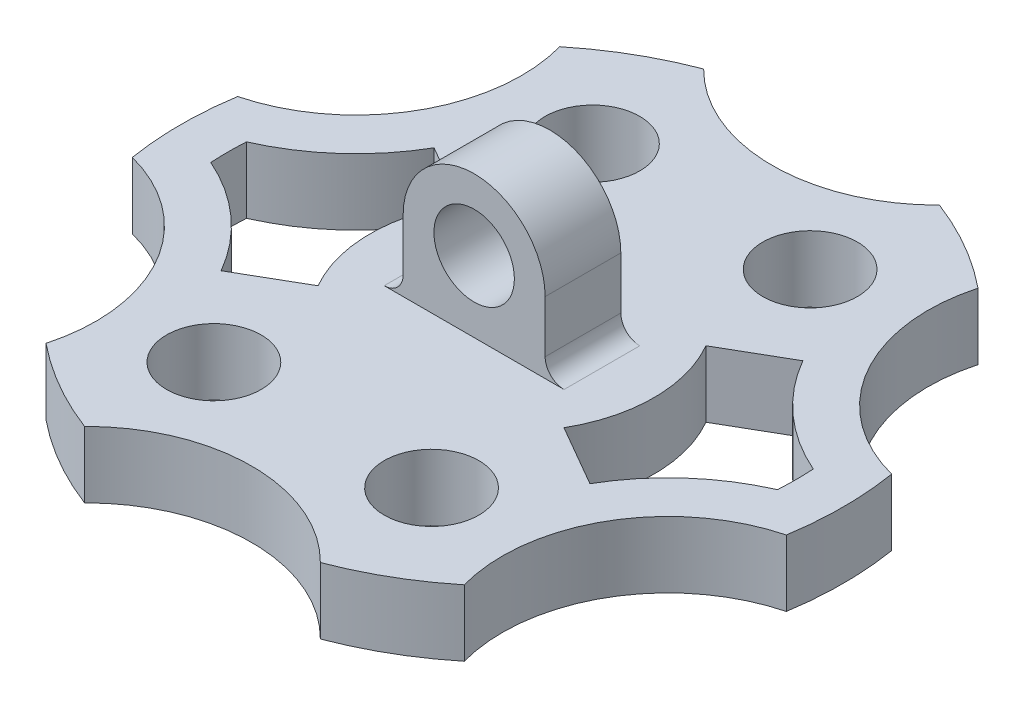
SolidWorks part; units mm, degrees
ref_plane "Front Plane" through (0, 0, 0) normal (0, 0, 1) x (1, 0, 0)
ref_plane "Top Plane" through (0, 0, 0) normal (0, 1, 0) x (1, 0, 0)
ref_plane "Right Plane" through (0, 0, 0) normal (1, 0, 0) x (0, 0, -1)
sketch "Sketch1" plane through (0, 0, 0) normal (0, 1, 0) x (1, 0, 0)
  circle A0 centre (0, 0) radius 35
  dimension "D1" = 70
extrude "Boss-Extrude1" add sketch "Sketch1" along normal blind 7
sketch "Sketch2" plane through (0, 7, 0) normal (0, 1, 0) x (1, 0, 0)
  line L0 (0, -45.6338) -> (0, 45.6338) construction
  circle A0 centre (0, 0) radius 45 construction
  circle A1 centre (0, 45) radius 17.5
  point P4 (0, 0)
  dimension "D1" = 90
  dimension "D2" = 17.5
extrude "Cut-Extrude1" cut sketch "Sketch2" against normal through all
pattern_circular "CirPattern1" count 6 over 360 about axis through (0, 7, 0) along (0, -1, 0) of "Cut-Extrude1" reverse direction yes
hole_wizard "Ø10.0 (10) Diameter Hole1" positions "Sketch6" profile "Sketch7" hole size "Ø10.0" standard "ISO" end condition through all
sketch "Sketch6" plane through (0, 7, 0) normal (0, 1, 0) x (1, 0, 0)
  line L0 (0, 0) -> (0, 27.5) construction
  line L3 (0, 0) -> (-35, 0) construction
  arc A0 (-12.4565, 32.7083) -> (12.4565, 32.7083) centre (0, 45) ccw construction
  arc A1 (-34.5545, 5.5665) -> (-34.5545, -5.5665) centre (0, 0) ccw construction
  point P0 (-11.5, 20)
  dimension "D1" = 23
  dimension "D2" = 40
sketch "Sketch7" plane through (-11.5, 7, -20) normal (1, 0, 0) x (0, 0, 1)
  line L0 (0, 0) -> (0, 7)
  line L1 (0, 7) -> (5, 7)
  line L2 (5, 7) -> (5, 0)
  line L5 (5, 0) -> (0, 0)
  line L11 (0, -6.35) -> (0, 107.95) construction
  dimension "Thru Hole Dia." = 10
  dimension "Thru Hole Depth" = 7
sketch "Sketch8" plane through (0, 7, 0) normal (0, 1, 0) x (1, 0, 0)
  line L1 (11.5, -20) -> (-11.5, -20) construction
  line L2 (11.5, -20) -> (11.5, 20) construction
  line L3 (11.5, 20) -> (-11.5, 20) construction
  line L4 (-11.5, -20) -> (-11.5, 20) construction
  line L5 (11.5, -20) -> (-11.5, 20) construction
  line L6 (11.5, 20) -> (-11.5, -20) construction
  point P0 (0, 0)
pattern_linear "LPattern1" count 2 spacing 23 along (1, 0, 0) count 2 spacing 40 along (0, 0, 1) of "Ø10.0 (10) Diameter Hole1"
sketch "Sketch9" plane through (0, 7, 0) normal (0, 1, 0) x (1, 0, 0)
  line L0 (12.9904, -7.5) -> (19.4856, -11.25)
  line L1 (12.9904, 7.5) -> (19.4856, 11.25)
  line L2 (38.9711, 22.5) -> (0, 0) construction
  line L3 (0, 0) -> (38.9711, -22.5) construction
  arc A12 (12.9904, -7.5) -> (12.9904, 7.5) centre (0, 0) ccw
  arc A24 (16.6086, 24.9831) -> (29.9403, 1.8919) centre (38.9711, 22.5) ccw
  arc A25 (16.6086, 24.9831) -> (13.3317, 26.875) centre (0, 0) ccw
  arc A26 (-13.3317, 26.875) -> (13.3317, 26.875) centre (0, 45) ccw
  arc A27 (-13.3317, 26.875) -> (-16.6086, 24.9831) centre (0, 0) ccw
  arc A28 (-29.9403, 1.8919) -> (-16.6086, 24.9831) centre (-38.9711, 22.5) ccw
  arc A29 (-29.9403, 1.8919) -> (-29.9403, -1.8919) centre (0, 0) ccw
  arc A30 (-16.6086, -24.9831) -> (-29.9403, -1.8919) centre (-38.9711, -22.5) ccw
  arc A31 (-16.6086, -24.9831) -> (-13.3317, -26.875) centre (0, 0) ccw
  arc A32 (13.3317, -26.875) -> (-13.3317, -26.875) centre (0, -45) ccw
  arc A33 (13.3317, -26.875) -> (16.6086, -24.9831) centre (0, 0) ccw
  arc A34 (29.9403, -1.8919) -> (16.6086, -24.9831) centre (38.9711, -22.5) ccw
  arc A35 (29.9403, -1.8919) -> (29.9403, 1.8919) centre (0, 0) ccw
  arc A36 (19.4856, 11.25) -> (29.9403, 1.8919) centre (38.9711, 22.5) ccw
  arc A46 (29.9403, -1.8919) -> (19.4856, -11.25) centre (38.9711, -22.5) ccw
  arc A47 (29.9403, -1.8919) -> (29.9403, 1.8919) centre (0, 0) ccw
  point P0 (0, 0)
  dimension "D2" = 30
  dimension "D1" = 5
extrude "Cut-Extrude2" cut sketch "Sketch9" against normal through all
mirror "Mirror1" about plane through (0, 0, 0) normal (1, 0, 0) of "Cut-Extrude2"
sketch "Sketch11" plane through (0, 0, 0) normal (0, 1, 0) x (1, 0, 0)
  line L1 (-7.5, -4) -> (7.5, -4)
  line L2 (-7.5, -4) -> (-7.5, 4)
  line L3 (-7.5, 4) -> (7.5, 4)
  line L4 (7.5, -4) -> (7.5, 4)
  line L5 (-7.5, -4) -> (7.5, 4) construction
  line L6 (-7.5, 4) -> (7.5, -4) construction
  point P0 (0, 0)
  dimension "D1" = 8
  dimension "D2" = 15
extrude "Boss-Extrude2" add sketch "Sketch11" along normal blind 22
fillet "Fillet1" 2 edges at (7.5, 22, 0) (-7.5, 22, 0) type full round first side face at (7.5, 14.5, 0) second side face at (-7.5, 14.5, 0) middle face at (0, 22, 0)
hole_wizard "M10 Tapped Hole1" positions "Sketch12" profile "Sketch13" tap size "M10" standard "ISO" end condition through all
sketch "Sketch12" plane through (0, 0, 4) normal (0, 0, 1) x (1, 0, 0)
  point P0 (0, 14.5)
sketch "Sketch13" plane through (0, 14.5, 4) normal (1, 0, 0) x (0, -1, 0)
  line L0 (0, 0) -> (0, 36.7083)
  line L1 (0, 36.7083) -> (4.25, 36.7083)
  line L2 (4.25, 36.7083) -> (4.25, 0)
  line L5 (4.25, 0) -> (0, 0)
  line L11 (0, -6.35) -> (0, 107.95) construction
  dimension "Thru Tap Drill Dia." = 8.5
  dimension "Thru Tap Drill Depth" = 36.7083
cosmetic thread "Hole Thread1" parameters "D2"=10
fillet "Fillet2" radius 2 2 edges at (-7.5, 7, 0) (7.5, 7, 0)
